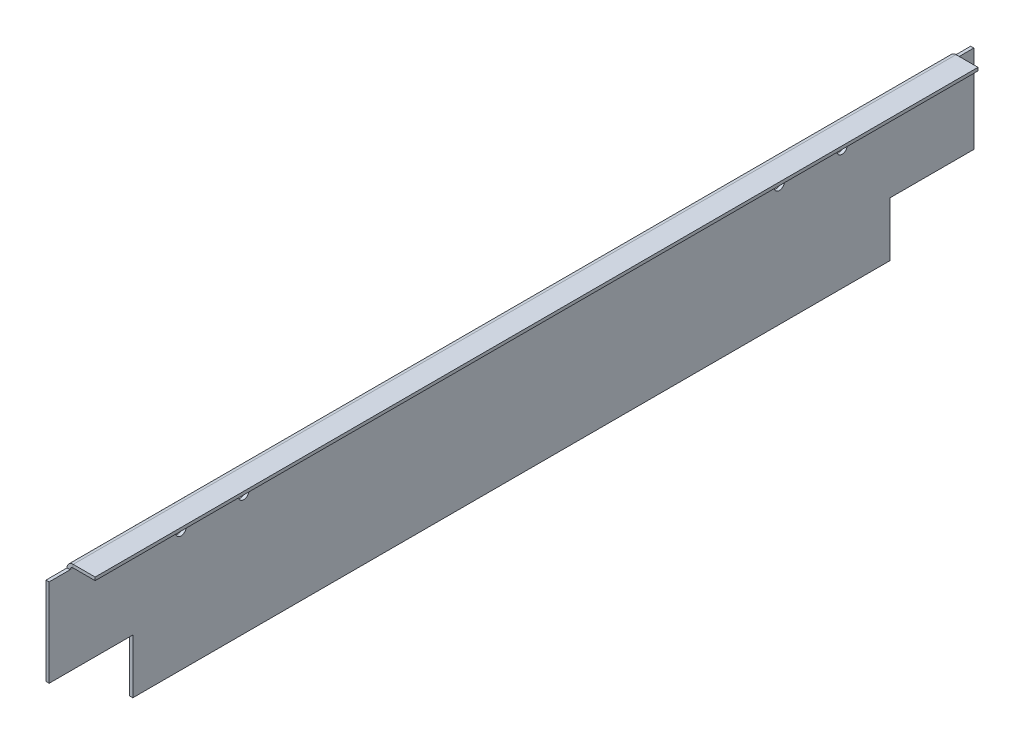
SolidWorks part; units mm, degrees
note: The reader was unsure of these and kept them because the rebuilt part matched: flange length of "Ребро-кромка1".
material "Оцинкованная сталь"
ref_plane "Спереди" through (0, 0, 0) normal (0, 0, 1) x (1, 0, 0)
ref_plane "Сверху" through (0, 0, 0) normal (0, 1, 0) x (1, 0, 0)
ref_plane "Справа" through (0, 0, 0) normal (1, 0, 0) x (0, 0, -1)
sketch "Эскиз1" plane through (0, 0, 0) normal (1, 0, 0) x (0, 0, -1)
  line L1 (-181, 0) -> (181, 0)
  line L2 (-181, 0) -> (-181, -68)
  line L3 (-181, -68) -> (181, -68)
  line L4 (181, 0) -> (181, -68)
  dimension "D1" = 68
  dimension "D2" = 362
base flange "Базовая кромка1" sketch "Эскиз1" thickness 1.5 reverse thickness direction no parameters "D1"=1.5
sketch "Эскиз6" plane through (0, 0, 0) normal (1, 0, 0) x (0, 0, -1)
  line L0 (181, -68) -> (181, 0) construction
  line L1 (181, 0) -> (-181, 0) construction
  line L5 (0, 50) -> (0, -50) construction
  circle A0 centre (158, -10) radius 2.5
  circle A2 centre (128, -10) radius 2.5
  circle A3 centre (-128, -10) radius 2.5
  circle A4 centre (-158, -10) radius 2.5
  dimension "D1" = 5
  dimension "D2" = 23
  dimension "D3" = 10
  dimension "D4" = 30
extrude "Вырез-Вытянуть1" cut sketch "Эскиз6" against normal blind 10
sketch "Эскиз7" plane through (0, 0, 0) normal (1, 0, 0) x (0, 0, -1)
  line L0 (-181, 0) -> (-181, -68) construction
  line L1 (-181, -42) -> (-221, -42)
  line L2 (-181, -42) -> (-181, 0)
  line L3 (-181, 0) -> (-221, 0)
  line L4 (-221, -42) -> (-221, 0)
  line L5 (-181, -68) -> (181, -68) construction
  line L7 (0, 50) -> (0, -50) construction
  line L8 (221, -42) -> (221, 0)
  line L9 (181, 0) -> (221, 0)
  line L10 (181, -42) -> (181, 0)
  line L11 (181, -42) -> (221, -42)
  dimension "D1" = 40
  dimension "D2" = 26
base flange "Выступ1" sketch "Эскиз7" thickness 1.5 reverse thickness direction no parameters "D1"=1.5
edge flange "Ребро-кромка1" sketch "Эскиз12" flange angle 90 flange length 12 flange position bend outside bend radius 1.5 thickness 1.5 relief rectangular parameters "D6"=10
sketch "Эскиз12" plane through (0, 0, 0) normal (0, -1, 0) x (0, 0, -1)
  line L0 (221, -1.5) -> (221, 0) construction
  line L2 (-211, 0) -> (-211, 12)
  line L3 (-211, 12) -> (211, 12)
  line L4 (211, 12) -> (211, 0)
  line L7 (221, 0) -> (-221, 0) construction
  line L8 (211, 0) -> (-211, 0)
  line L9 (-221, -1.5) -> (-221, 0) construction
  dimension "D1" = 10
  dimension "D2" = 10
bend "EdgeBend1" bend radius 1.5 bend angle 90 parameters "D5"=1
sketch "Сгиб-Линии1" [suppressed] plane through (0, 0, 0) normal (0, 1, 0) x (1, 0, 0)
sketch "Граничная рамка1" [suppressed] plane through (0, 0, 0) normal (0, 1, 0) x (1, 0, 0)
sheet metal parameters "Листовой металл3" thickness 1.5 parameters "D1"=2
flat pattern "Развертка3" [suppressed]
sketch "Сгиб-Линии2" plane through (0, 0, 0) normal (0, 1, 0) x (1, 0, 0)
sketch "Граничная рамка2" [suppressed] plane through (0, 0, 0) normal (0, 1, 0) x (1, 0, 0)
sheet metal parameters "Листовой металл4" thickness 1.5 parameters "D1"=2
flat pattern "Развертка3"
sketch "Сгиб-Линии2" plane through (0, 0, 0) normal (0, 1, 0) x (1, 0, 0)
sketch "Граничная рамка2" [suppressed] plane through (0, 0, 0) normal (0, 1, 0) x (1, 0, 0)
sheet metal parameters "Листовой металл5" thickness 1.5 parameters "D1"=2
flat pattern "Развертка5"
sketch "Сгиб-Линии3" plane through (0, 0, 0) normal (0, 1, 0) x (1, 0, 0)
sketch "Граничная рамка3" [suppressed] plane through (0, 0, 0) normal (0, 1, 0) x (1, 0, 0)
sheet metal parameters "Листовой металл6" thickness 1.5 parameters "D1"=2
flat pattern "Развертка5"
sketch "Сгиб-Линии3" plane through (0, 0, 0) normal (1, 0, 0) x (0, 0, -1)
  line L0 (211, 1.7671) -> (-211, 1.7671) construction
  line L1 (211, 1.7671) -> (-211, 1.7671) construction
sketch3d "Граничная рамка3" [suppressed]
  line L0 (-221, -68, 0) -> (221, -68, 0) construction
  line L1 (-221, 14.0343, 0) -> (221, 14.0343, 0) construction
  line L2 (-221, -68, 0) -> (-221, 14.0343, 0) construction
  line L3 (221, -68, 0) -> (221, 14.0343, 0) construction
bend of the flat pattern "Плоское состояние-<EdgeBend1>1"
